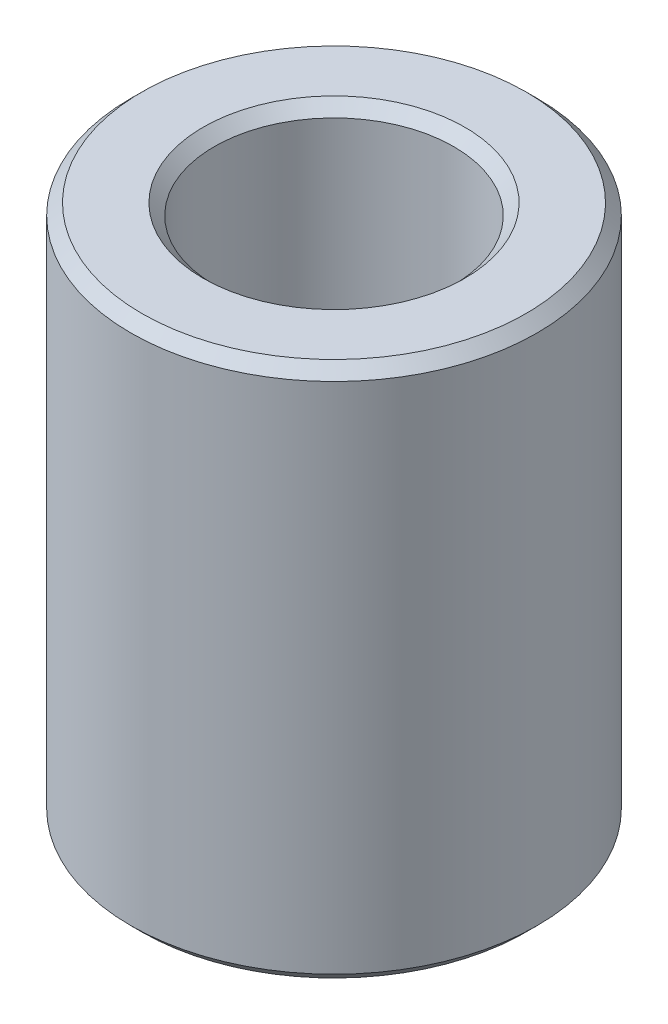
SolidWorks part; units mm, degrees
ref_plane "Front Plane" through (0, 0, 0) normal (0, 0, 1) x (1, 0, 0)
ref_plane "Top Plane" through (0, 0, 0) normal (0, 1, 0) x (1, 0, 0)
ref_plane "Right Plane" through (0, 0, 0) normal (1, 0, 0) x (0, 0, -1)
sketch "Sketch1" plane through (0, 0, 0) normal (0, 1, 0) x (1, 0, 0)
  circle A0 centre (0, 0) radius 37.5
  dimension "SLEEVE_OD" = 75
extrude "Boss-Extrude1" add sketch "Sketch1" along normal blind 98.8561
sketch "Sketch2" plane through (0, 0, 0) normal (0, 1, 0) x (1, 0, 0)
  circle A0 centre (0, 0) radius 22.0927
  dimension "BORE_D" = 44.1855
extrude "Cut-Extrude1" cut sketch "Sketch2" along normal through all
chamfer "Chamfer1" distance 2.0638 angle 45 4 edges at (0, 98.8561, 22.0927) (0, 0, 22.0927) (0, 0, 37.5) (0, 98.8561, 37.5)
